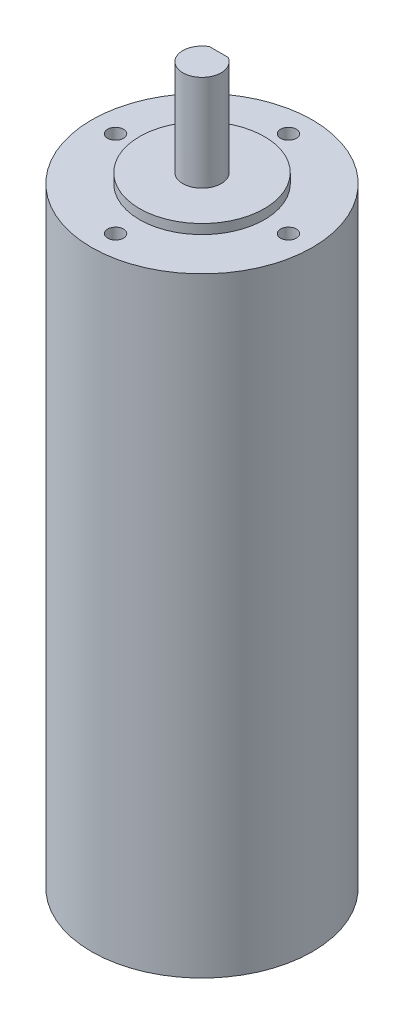
SolidWorks part; units mm, degrees
ref_plane "Front Plane" through (0, 0, 0) normal (0, 0, 1) x (1, 0, 0)
ref_plane "Top Plane" through (0, 0, 0) normal (0, 1, 0) x (1, 0, 0)
ref_plane "Right Plane" through (0, 0, 0) normal (1, 0, 0) x (0, 0, -1)
sketch "Sketch2" plane through (0, 0, 0) normal (0, 1, 0) x (1, 0, 0)
  circle A0 centre (0, 0) radius 23
  dimension "D1" = 46
extrude "Boss-Extrude1" add sketch "Sketch2" along normal blind 127
sketch "Sketch3" plane through (0, 127, 0) normal (0, 1, 0) x (1, 0, 0)
  circle A0 centre (0, 0) radius 13
  dimension "D1" = 26
extrude "Boss-Extrude2" add sketch "Sketch3" along normal blind 2
sketch "Sketch4" plane through (0, 129, 0) normal (0, 1, 0) x (1, 0, 0)
  circle A0 centre (0, 0) radius 4
  dimension "D1" = 8
extrude "Boss-Extrude3" add sketch "Sketch4" along normal blind 20
sketch "Sketch8" plane through (0, 127, 0) normal (0, 1, 0) x (1, 0, 0)
  circle A0 centre (0, 18) radius 1.65
  circle A1 centre (18, 0) radius 1.65
  circle A2 centre (0, -18) radius 1.65
  circle A3 centre (-18, 0) radius 1.65
  point P11 (0, 0)
  dimension "D1" = 3.3
  dimension "D3" = 18
  dimension "D2" = 4
extrude "Cut-Extrude1" cut sketch "Sketch8" against normal blind 10
sketch "Sketch10" plane through (0, 149, 0) normal (0, 1, 0) x (1, 0, 0)
  line L0 (-1.9365, 3.5) -> (1.9365, 3.5)
  circle A0 centre (0, 0) radius 4 construction
  circle A1 centre (0, 0) radius 4
  point P5 (0, 3.5)
  circle M2 centre (0, 0) radius 4
  dimension "D3" = 8
  dimension "D1" = 3.5
  dimension "D2" = 0
extrude "Cut-Extrude2" cut sketch "Sketch10" against normal blind 15 contours L0 M2 region at (0, 149, -3.7011)
